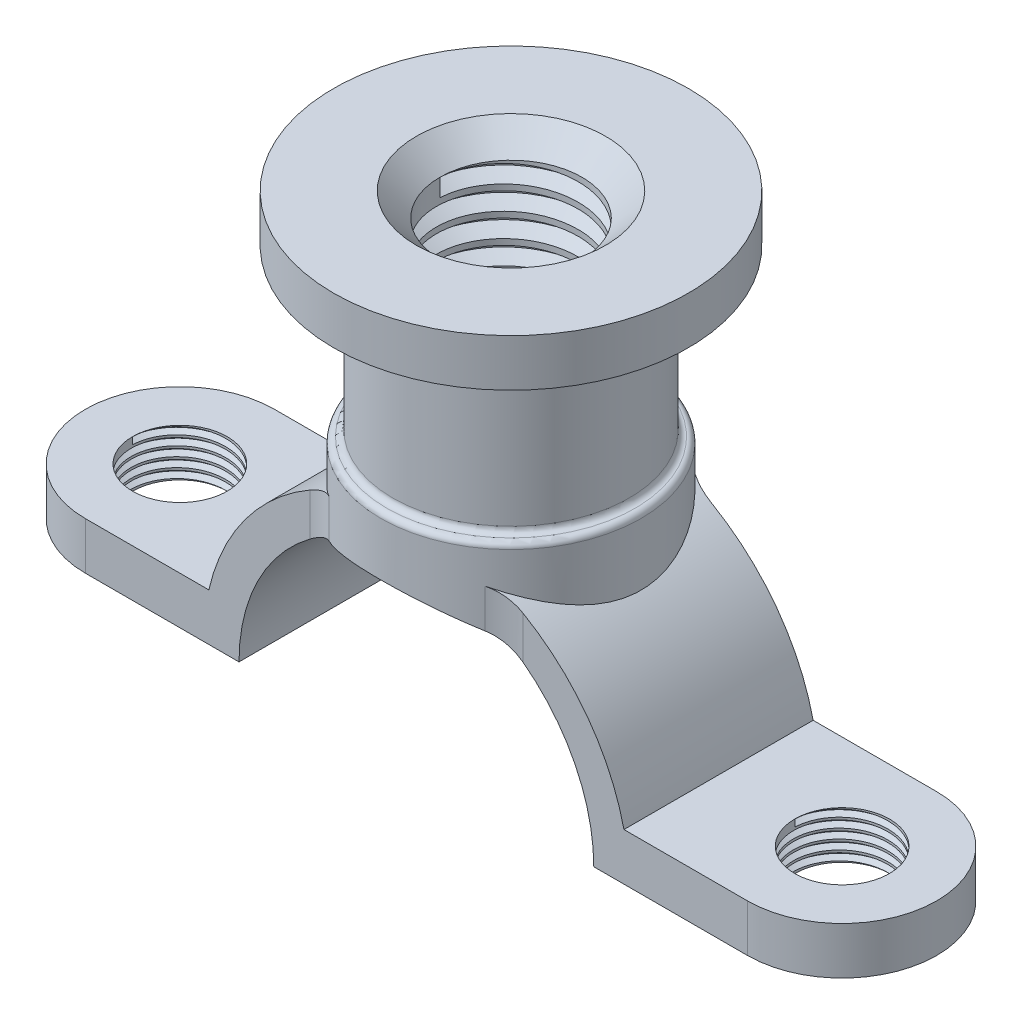
SolidWorks part; units mm, degrees
material "Brass"
ref_plane "Front Plane" through (0, 0, 0) normal (0, 0, 1) x (1, 0, 0)
ref_plane "Top Plane" through (0, 0, 0) normal (0, 1, 0) x (1, 0, 0)
ref_plane "Right Plane" through (0, 0, 0) normal (1, 0, 0) x (0, 0, -1)
sketch "Sketch2" plane through (0, 0, 0) normal (0, 0, 1) x (1, 0, 0)
  circle A0 centre (0, 0) radius 7.5
  circle A1 centre (0, 0) radius 9
  dimension "D1" = 15
  dimension "D2" = 18
extrude "Boss-Extrude1" add sketch "Sketch2" along normal mid plane 8
sketch "Sketch3" plane through (0, 0, 0) normal (0, 1, 0) x (1, 0, 0)
  line L0 (9, 4) -> (14, 4)
  line L1 (9, -4) -> (14, -4)
  line L2 (9, -4) -> (9, 4) construction
  line L3 (9, 4) -> (7.5, 4)
  line L4 (9, 4) -> (-9, 4) construction
  line L5 (7.5, 4) -> (-7.5, 4) construction
  line L6 (7.5, 4) -> (7.5, -4)
  line L7 (7.5, -4) -> (9, -4)
  arc A0 (14, 4) -> (14, -4) centre (14, 0) cw
  circle A1 centre (14, 0) radius 2
  dimension "D2" = 4
  dimension "D1" = 5
extrude "Boss-Extrude2" add sketch "Sketch3" along normal blind 2 contours A0 L0 L3 L6 L7 L1 A1 region at (11.5, 0, -3.868)
mirror "Mirror1" about plane through (0, 0, 0) normal (1, 0, 0) of "Boss-Extrude2", "Boss-Extrude1"
sketch "Sketch4" plane through (0, 0, 0) normal (0, 0, 1) x (1, 0, 0)
  line L0 (4.4, 0) -> (-4.4, 0) construction
  line L1 (-10.3155, 0) -> (19.4076, 0)
  line L2 (-10.3155, 0) -> (-10.3155, -9.5955)
  line L3 (-10.3155, -9.5955) -> (19.4076, -9.5955)
  line L4 (19.4076, 0) -> (19.4076, -9.5955)
extrude "Cut-Extrude2" cut sketch "Sketch4" against normal mid plane 10
ref_plane "Plane4" through (0, 6, 0) normal (0, 1, 0) x (1, 0, 0)
sketch "Sketch5" plane through (0, 6, 0) normal (0, 1, 0) x (1, 0, 0)
  circle A0 centre (0, 0) radius 5.5
  dimension "D1" = 11
extrude "Boss-Extrude4" add sketch "Sketch5" along normal blind 4
sketch "Sketch6" plane through (0, 10, 0) normal (0, 1, 0) x (1, 0, 0)
  circle A0 centre (0, 0) radius 5
  dimension "D1" = 10
extrude "Boss-Extrude5" add sketch "Sketch6" along normal blind 7
sketch "Sketch7" plane through (0, 17, 0) normal (0, 1, 0) x (1, 0, 0)
  circle A0 centre (0, 0) radius 7.5
  dimension "D1" = 15
extrude "Boss-Extrude6" add sketch "Sketch7" along normal blind 2
sketch "Sketch8" plane through (0, 19, 0) normal (0, 1, 0) x (1, 0, 0)
  circle A0 centre (0, 0) radius 3
  dimension "D1" = 6
fillet "Fillet1" radius 1 1 edges at (0, 17, 5)
extrude "Boss-Extrude7" add sketch "Sketch5<2>" along normal blind 3
sketch "Sketch5<2>" plane through (0, 6, 0) normal (0, 1, 0) x (1, 0, 0) same geometry as "Sketch5"
extrude "Cut-Extrude4" cut sketch "Sketch8" against normal through all contours A0
chamfer "Chamfer2" distance 1 angle 45 1 edges at (0, 19, 3)
thread "Thread1" pitch 1 method cut profile "Thread Profile1" start angle 0, offset 0, length 8, pitch 1, diameter 6
ref_plane "Plane5" through (-3, 18, 0) normal (0, 0, 1) x (-1, 0, 0)
sketch "Thread Profile1" plane through (-3, 18, 0) normal (0, 0, 1) x (-1, 0, 0)
  line L0 (0, 0) -> (0, 1) construction
  line L1 (0, 0) -> (0.5413, 0.3125)
  line L2 (0.5413, 0.3125) -> (0.5413, 0.4375)
  line L3 (0.5413, 0.4375) -> (0, 0.75)
  line L4 (0.5413, 0.375) -> (0, 0.375) construction
  line L11 (0, 0) -> (0, 0.75)
  point P2 (0, 0)
  dimension "Pitch" = 1
  dimension "Profile_Angle" = 60
  dimension "Profile_Land" = 0.125
  dimension "Profile_Height" = 0.5413
sketch "Sketch11" plane through (0, 6, 0) normal (0, 1, 0) x (1, 0, 0)
  circle A0 centre (0, 0) radius 3.5
  dimension "D1" = 7
extrude "Cut-Extrude5" cut sketch "Sketch11" against normal mid plane 4
fillet "Fillet10" radius 2 1 edges at (0, 8, 3.5)
sketch "Sketch12" plane through (0, 0, 0) normal (0, 0, 1) x (1, 0, 0)
  circle A0 centre (0, 0) radius 7.5
extrude "Cut-Extrude6" cut sketch "Sketch12" against normal mid plane 20
thread "Thread2" pitch 0.4 method cut profile "Thread Profile2" start angle 0, offset 0, length 8, pitch 0.4, diameter 4
ref_plane "Plane6" through (-16, 2, 0) normal (0, 0, 1) x (-1, 0, 0)
sketch "Thread Profile2" plane through (-16, 2, 0) normal (0, 0, 1) x (-1, 0, 0)
  line L0 (0, 0) -> (0, 0.4) construction
  line L1 (0, 0) -> (0.2165, 0.125)
  line L2 (0.2165, 0.125) -> (0.2165, 0.175)
  line L3 (0.2165, 0.175) -> (0, 0.3)
  line L4 (0.2165, 0.15) -> (0, 0.15) construction
  line L11 (0, 0) -> (0, 0.3)
  point P2 (0, 0)
  dimension "Pitch" = 0.4
  dimension "Profile_Angle" = 60
  dimension "Profile_Land" = 0.05
  dimension "Profile_Height" = 0.2165
thread "Thread3" pitch 0.4 method cut profile "Thread Profile3" start angle 0, offset 0, length 8, pitch 0.4, diameter 4
ref_plane "Plane7" through (12, 2, 0) normal (0, 0, 1) x (-1, 0, 0)
sketch "Thread Profile3" plane through (12, 2, 0) normal (0, 0, 1) x (-1, 0, 0)
  line L0 (0, 0) -> (0, 0.4) construction
  line L1 (0, 0) -> (0.2165, 0.125)
  line L2 (0.2165, 0.125) -> (0.2165, 0.175)
  line L3 (0.2165, 0.175) -> (0, 0.3)
  line L4 (0.2165, 0.15) -> (0, 0.15) construction
  line L11 (0, 0) -> (0, 0.3)
  point P2 (0, 0)
  dimension "Pitch" = 0.4
  dimension "Profile_Angle" = 60
  dimension "Profile_Land" = 0.05
  dimension "Profile_Height" = 0.2165
fillet "Fillet14" radius 2 4 edges at (3.7749, 7.3254, 4) (3.7749, 7.3254, -4) (-3.7749, 7.3254, -4) (-3.7749, 7.3254, 4)
fillet "Fillet15" radius 0.25 2 edges at (0, 10, 5) (0, 10, 5.5)
